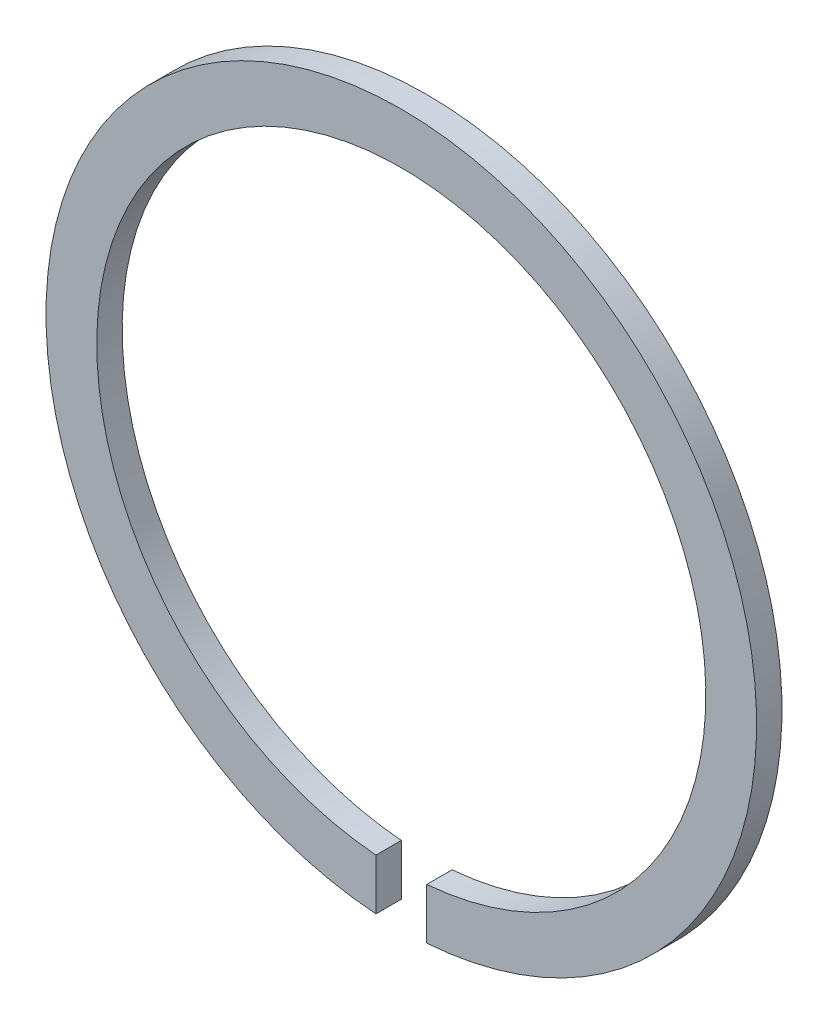
SolidWorks part; units mm, degrees
ref_plane "Plan de face" through (0, 0, 0) normal (0, 0, 1) x (1, 0, 0)
ref_plane "Plan de dessus" through (0, 0, 0) normal (0, 1, 0) x (1, 0, 0)
ref_plane "Plan de droite" through (0, 0, 0) normal (1, 0, 0) x (0, 0, -1)
sketch "Esquisse2" plane through (0, 0, 0) normal (0, 0, 1) x (1, 0, 0)
  line L0 (0, 0) -> (0, -4.3237) construction
  line L1 (0.5, -5.9791) -> (0.5, -6.9821)
  line L2 (-0.5, -5.9791) -> (-0.5, -6.9821)
  arc A0 (0.5, -6.9821) -> (-0.5, -6.9821) centre (0, 0) ccw
  arc A1 (0.5, -5.9791) -> (-0.5, -5.9791) centre (0, 0) ccw
  dimension "D1" = 14
  dimension "D2" = 12
  dimension "D3" = 0.5
extrude "Boss.-Extru.1" add sketch "Esquisse2" along normal blind 0.5
